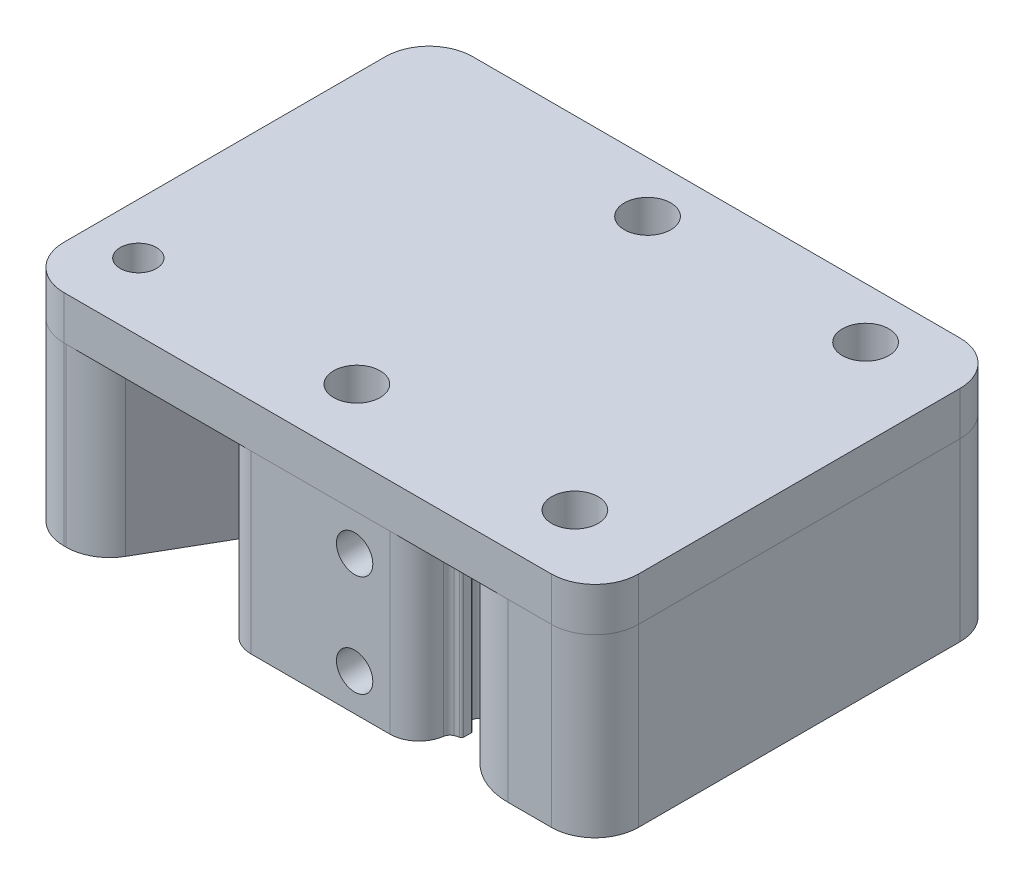
SolidWorks part; units mm, degrees
material "AISI 1045 Steel, cold drawn"
ref_plane "Front Plane" through (0, 0, 0) normal (0, 0, 1) x (1, 0, 0)
ref_plane "Top Plane" through (0, 0, 0) normal (0, 1, 0) x (1, 0, 0)
ref_plane "Right Plane" through (0, 0, 0) normal (1, 0, 0) x (0, 0, -1)
sketch "Sketch1" plane through (0, 0, 0) normal (0, 1, 0) x (1, 0, 0)
  line L0 (-13.5, -13.5) -> (-13.5, -14.619)
  line L1 (7.5, -10) -> (-7.5, -10) construction
  line L2 (7.5, -10) -> (7.5, 10) construction
  line L3 (7.5, 10) -> (-7.5, 10) construction
  line L4 (-7.5, -10) -> (-7.5, 10) construction
  line L5 (7.5, -10) -> (-7.5, 10) construction
  line L6 (7.5, 10) -> (-7.5, -10) construction
  line L7 (13.5, -13.5) -> (-13.5, -13.5) construction
  line L8 (13.5, -13.5) -> (13.5, 13.5)
  line L9 (13.5, 13.5) -> (-13.5, 13.5)
  line L10 (-13.5, -13.5) -> (-13.5, 13.5)
  line L11 (13.5, -13.5) -> (-13.5, 13.5) construction
  line L12 (13.5, 13.5) -> (-13.5, -13.5) construction
  line L13 (-13.5, -14.619) -> (13.5, -14.619)
  line L14 (13.5, -14.619) -> (13.5, -13.5)
  point P0 (0, 0)
  point P6 (0, 0)
  dimension "D1" = 15
  dimension "D2" = 27
  dimension "D3" = 1.119
  dimension "D4" = 20
extrude "Boss-Extrude1" add sketch "Sketch1" along normal mid plane 12.1
hole_wizard "M3 Clearance Hole1" positions "Sketch2" profile "Sketch3" hole size "M3" standard "ANSI Metric" end condition through all
sketch "Sketch2" plane through (0, 6.05, 0) normal (0, 1, 0) x (1, 0, 0)
  point P0 (-7.5, 10)
  point P3 (7.5, 10)
  point P6 (7.5, -10)
  point P9 (-7.5, -10)
sketch "Sketch3" plane through (-7.5, 6.05, -10) normal (1, 0, 0) x (0, 0, 1)
  line L0 (0, 0) -> (0, 12.1)
  line L1 (0, 12.1) -> (1.6, 12.1)
  line L2 (1.6, 12.1) -> (1.6, 0)
  line L5 (1.6, 0) -> (0, 0)
  line L11 (0, -6.35) -> (0, 107.95) construction
  dimension "Thru Hole Dia." = 3.2
  dimension "Thru Hole Depth" = 12.1
sketch "Sketch6" plane through (0, 6.05, 0) normal (0, 1, 0) x (1, 0, 0)
  line L0 (13.5, 13.5) -> (-13.5, 13.5) construction
  line L1 (-13.5, -14.619) -> (-28, -14.619)
  line L2 (-13.5, -14.619) -> (-13.5, 13.5)
  line L3 (-13.5, 13.5) -> (-28, 13.5)
  line L4 (-28, -14.619) -> (-28, 13.5)
  dimension "D1" = 28
extrude "Boss-Extrude3" add sketch "Sketch6" against normal up to surface (12.1 mm away) up to face at (-7.5, -6.05, -8.4)
sketch "Sketch8" plane through (0, 6.05, 0) normal (0, 1, 0) x (1, 0, 0)
  line L0 (-28, -14.619) -> (13.5, -14.619) construction
  line L2 (2.881, -10) -> (2.881, 4)
  line L3 (2.881, 4) -> (1.361, 4)
  line L4 (1.361, -14.619) -> (1.361, 4)
  line L5 (7.5, -14.619) -> (1.361, -14.619)
  arc A0 (2.881, -10) -> (7.5, -14.619) centre (7.5, -10) ccw
  dimension "D1" = 1.52
  dimension "D2" = 14
extrude "Cut-Extrude2" cut sketch "Sketch8" against normal up to surface (12.1 mm away) up to face at (-7.5, -6.05, -8.4)
sketch "Sketch9" plane through (0, 6.05, 0) normal (0, 1, 0) x (1, 0, 0)
  line L1 (2.881, 4) -> (6.306, 4)
  line L2 (2.881, 4) -> (2.881, -8)
  line L3 (2.881, -8) -> (6.306, -8)
  line L4 (6.306, 4) -> (6.306, -8)
  dimension "D1" = 3.425
  dimension "D2" = 12
extrude "Cut-Extrude3" cut sketch "Sketch9" against normal up to surface (12.1 mm away) up to face at (-7.5, -6.05, -8.4)
sketch "Sketch11" plane through (0, 6.05, 0) normal (0, 1, 0) x (1, 0, 0)
  line L1 (2.111, 0.7046) -> (2.111, 4.8734) construction
  line L4 (2.365, -998.8465) -> (2.365, 49001.1535) construction
  line L5 (2.111, 2.2598) -> (2.111, 2)
  line L6 (1.361, 3) -> (2.111, 3) construction
  line L7 (1.361, 4) -> (1.361, -14.619) construction
  line L8 (6.306, 4) -> (1.361, 4) construction
  line L9 (2.111, 2) -> (1.361, 2)
  line L10 (1.361, 2) -> (1.361, 4)
  line L11 (2.111, 4) -> (1.361, 4)
  line L12 (2.111, 3.7402) -> (2.111, 4)
  arc A2 (1.6728, 3.4989) -> (1.6728, 2.5011) centre (1.916, 3) ccw
  arc A4 (1.6728, 2.5011) -> (1.9806, 2.4085) centre (2.111, 3.4) ccw
  arc A5 (2.111, 2.2598) -> (1.9806, 2.4085) centre (1.961, 2.2598) ccw
  arc A6 (2.111, 3.7402) -> (1.9806, 3.5915) centre (1.961, 3.7402) cw
  arc A7 (1.6728, 3.4989) -> (1.9806, 3.5915) centre (2.111, 2.6) cw
  point P7 (1.361, 3)
  line M19 (1.361, -14.619) -> (1.361, 4)
  line M20 (1.361, 4) -> (6.306, 4)
  dimension "D3" = 0.555
  dimension "D4" = 1
  dimension "D5" = 1
  dimension "D6" = 0.15
  dimension "D1" = 0.254
  dimension "D2" = 0.75
  dimension "D7" = 1
extrude "Boss-Extrude4" add sketch "Sketch11" against normal up to surface (12.1 mm away) contours A2 A7 A6 L12 L10 M20 | L5 A5 A4 A2 L9 M19 region at (1.6833, 6.05, -3.7249) region at (1.6833, 6.05, -2.2751) up to face at (-7.5, -6.05, -8.4)
pattern_linear "LPattern1" count 9 spacing 2 along (0, 0, 1) of "Boss-Extrude4"
sketch "Sketch12" plane through (0, 6.05, 0) normal (0, 1, 0) x (1, 0, 0)
  circle A0 centre (2.111, 4) radius 0.5
  circle A1 centre (6.306, 4) radius 0.5
  circle A2 centre (6.306, -8) radius 0.5
  dimension "D1" = 1
extrude "Cut-Extrude5" cut sketch "Sketch12" against normal up to surface (12.1 mm away) up to face at (1.556, -6.05, 5.2005)
sketch "Sketch13" plane through (0, 6.05, 0) normal (0, 1, 0) x (1, 0, 0)
  line L3 (2.111, -14) -> (1.361, -14) construction
  line L4 (2.111, -13.7402) -> (2.111, -14) construction
  line L5 (2.111, -14) -> (1.361, -14)
  line L6 (2.111, -13.7402) -> (2.111, -14)
  line L7 (1.361, -14) -> (1.361, -13)
  arc A6 (1.6728, -12.5011) -> (1.6728, -13.4989) centre (1.916, -13) ccw construction
  arc A7 (1.6728, -13.4989) -> (1.9806, -13.5915) centre (2.111, -12.6) ccw construction
  arc A8 (2.111, -13.7402) -> (1.9806, -13.5915) centre (1.961, -13.7402) ccw construction
  arc A9 (1.361, -13) -> (1.6728, -13.4989) centre (1.916, -13) ccw
  arc A10 (1.6728, -13.4989) -> (1.9806, -13.5915) centre (2.111, -12.6) ccw
  arc A11 (2.111, -13.7402) -> (1.9806, -13.5915) centre (1.961, -13.7402) ccw
extrude "Cut-Extrude6" cut sketch "Sketch13" against normal up to surface (12.1 mm away) up to face at (1.6903, -6.05, 5.2284)
fillet "Fillet3" radius 0.5 7 edges at (5.806, 0, 8) (6.306, 0, 7.5) (5.806, 0, -4) (6.306, 0, -3.5) (2.611, 0, -4) (1.8595, 0, -3.5679) (2.881, 0, 8)
sketch "Sketch17" plane through (0, 6.05, 0) normal (0, 1, 0) x (1, 0, 0)
  line L0 (-21.1595, -14.619) -> (-15.513, -17.879)
  line L11 (-6.4019, 5.9019) -> (-3.8038, 4.4019) construction
  line L12 (-6.4019, 5.9019) -> (-2.9019, 11.9641) construction
  line L13 (-3.8038, 4.4019) -> (-0.3038, 10.4641) construction
  line L14 (-2.9019, 11.9641) -> (-0.3038, 10.4641) construction
  line L15 (-4.201, 12.7141) -> (0.9952, 9.7141) construction
  line L16 (-4.201, 12.7141) -> (-2.701, 15.3122) construction
  line L17 (0.9952, 9.7141) -> (2.4952, 12.3122) construction
  line L18 (-2.701, 15.3122) -> (2.4952, 12.3122) construction
  line L19 (-5.1029, 5.1519) -> (-0.1029, 13.8122) construction
  line L20 (-21.1595, -14.619) -> (-8.5843, 7.1619)
  line L21 (-15.513, -17.879) -> (-2.9378, 3.9019)
  line L22 (-8.5843, 7.1619) -> (-2.9378, 3.9019)
  line L23 (-22.5782, -10.8263) -> (-19.8719, -12.3888) construction
  line L24 (-22.5782, -10.8263) -> (-12.5782, 6.4942) construction
  line L25 (-19.8719, -12.3888) -> (-9.8719, 4.9317) construction
  line L26 (-12.5782, 6.4942) -> (-9.8719, 4.9317) construction
  line L27 (-28, -14.619) -> (1.361, -14.619) construction
  line L28 (-14.8719, -3.7285) -> (-17.5782, -2.166) construction
  circle A0 centre (-7.5, 10) radius 1.6 construction
  circle A1 centre (-7.5, -10) radius 1.6 construction
  dimension "D1" = 6.52
  dimension "D3" = 3
  dimension "D10" = 3
  dimension "D2" = 6
  dimension "D4" = 3
  dimension "D5" = 10
  dimension "D6" = 3.125
  dimension "D7" = 2.5
  dimension "D8" = 60
  dimension "D9" = 3
  dimension "D11" = 20
extrude "Cut-Extrude7" cut sketch "Sketch17" against normal up to surface (12.1 mm away) up to face at (1.9594, -6.05, 4.4571)
sketch "Sketch18" plane through (0, 6.05, 0) normal (0, 1, 0) x (1, 0, 0)
  line L0 (-26.0342, -14.619) -> (-26.0342, -10)
  line L2 (-14.1485, 10.3744) -> (-26.7237, -11.4065)
  line L3 (-12.344, 13.5) -> (-24.1063, -6.8729)
  line L4 (-12.344, 13.5) -> (-28, 13.5)
  line L5 (-28, 13.5) -> (-28, -14.619)
  line L7 (-28, -14.619) -> (-21.1595, -14.619) construction
  line L8 (-8.5843, 7.1619) -> (-21.1595, -14.619) construction
  line L10 (-28, -14.619) -> (-26.0342, -14.619)
  arc A2 (-24.1063, -6.8729) -> (-26.0342, -10) centre (-22.5342, -10) ccw
  point P0 (-7.5, -10)
  dimension "D2" = 3.5
  dimension "D1" = 6.425
extrude "Cut-Extrude8" cut sketch "Sketch18" against normal up to surface (12.1 mm away) contours A2 L10 | A2 L3 L4 L5 L10 region at (-22.8632, 6.05, -4.1187) up to face at (1.2277, -6.05, 4.4618)
hole_wizard "M3 Clearance Hole2" positions "Sketch19" profile "Sketch20" hole size "M3" standard "ANSI Metric" end condition up to next
sketch "Sketch19" plane through (0, 6.05, 0) normal (0, 1, 0) x (1, 0, 0)
  point P0 (-22.5342, -10)
sketch "Sketch20" plane through (-22.5342, 6.05, 10) normal (1, 0, 0) x (0, 0, 1)
  line L0 (0, 0) -> (0, 12.1)
  line L1 (0, 12.1) -> (1.6, 12.1)
  line L2 (1.6, 12.1) -> (1.6, 0)
  line L5 (1.6, 0) -> (0, 0)
  line L11 (0, -6.35) -> (0, 107.95) construction
  dimension "Thru Hole Dia." = 3.2
  dimension "Thru Hole Depth" = 12.1
fillet "Fillet4" radius 3 5 edges at (13.5, 0, 14.619) (13.5, 0, -13.5) (-12.344, 0, -13.5) (-26.0342, 0, 14.619) (-21.1595, 0, 14.619)
sketch "Sketch21" plane through (0, 6.05, 0) normal (0, 1, 0) x (1, 0, 0)
  line L0 (-8.5843, 7.1619) -> (-20.2935, -13.119) construction
  line L1 (-17.8343, -8.8595) -> (-20.8004, -7.147)
  line L2 (-17.8343, -8.8595) -> (-9.3343, 5.8629)
  line L3 (-20.8004, -7.147) -> (-12.3004, 7.5754)
  line L4 (-9.3343, 5.8629) -> (-12.3004, 7.5754)
  line L5 (-2.9378, 3.9019) -> (-8.5843, 7.1619) construction
  dimension "D3" = 17
  dimension "D1" = 3.425
  dimension "D2" = 1.5
extrude "Cut-Extrude9" cut sketch "Sketch21" against normal up to surface (12.1 mm away) up to face at (-22.5342, -6.05, 11.6)
sketch "Sketch22" plane through (0, 6.05, 0) normal (0, 1, 0) x (1, 0, 0)
  circle A0 centre (-20.8004, -7.147) radius 0.5
  circle A1 centre (-12.3004, 7.5754) radius 0.5
  circle A2 centre (-8.5843, 7.1619) radius 0.5
  circle A3 centre (-2.9378, 3.9019) radius 0.5
  arc A4 (2.544, 4.25) -> (1.6303, 3.8625) centre (2.111, 4) ccw construction
extrude "Cut-Extrude10" cut sketch "Sketch22" against normal up to surface (12.1 mm away) up to face at (-22.5342, -6.05, 11.6)
fillet "Fillet5" radius 0.5 10 edges at (-17.8343, 0, 8.8595) (-3.1878, 0, -3.4689) (-3.3708, 0, -4.1519) (-8.8343, 0, -6.7289) (-8.1513, 0, -6.9119) (-11.8674, 0, -7.3254) (-12.5504, 0, -7.1424) (-20.5504, 0, 6.714) (-20.3674, 0, 7.397) (-9.3343, 0, -5.8629)
ref_plane "Plane2" through (6.9551, 0, -12.0466) normal (0.5, 0, -0.866) x (-0.866, 0, -0.5)
hole_wizard "CBORE for M3 SHCS1" positions "Sketch23" profile "Sketch25" counterbore size "M3" standard "ANSI Metric" end condition up to next
sketch "Sketch23" plane through (6.9551, 0, -12.0466) normal (0.5, 0, -0.866) x (-0.866, 0, -0.5)
  line L0 (4.4952, -6.05) -> (9.4952, 6.05) construction
  line L1 (-2.3433, -6.05) -> (15.9402, -6.05) construction
  line L3 (-2.3433, 6.05) -> (15.9402, 6.05) construction
  point P15 (6.9952, 0)
  dimension "D1" = 5
sketch "Sketch25" plane through (0.8971, 0, -15.5442) normal (0, 1, 0) x (-0.866, 0, -0.5)
  line L0 (0, 0) -> (0, 12)
  line L1 (0, 12) -> (1.6, 12)
  line L3 (1.6, 12) -> (1.6, 6)
  line L4 (1.6, 6) -> (3.25, 6)
  line L5 (3.25, 6) -> (3.25, 0)
  line L7 (3.25, 0) -> (0, 0)
  line L11 (0, -6.35) -> (0, 107.95) construction
  dimension "Thru Hole Dia." = 3.2
  dimension "Thru Hole Depth" = 12
  dimension "C'Bore Dia." = 6.5
  dimension "C'Bore Depth" = 6
sketch "Sketch30" plane through (0, 6.05, 0) normal (0, 1, 0) x (1, 0, 0)
  line L1 (3.381, -8) -> (5.44, -8) construction
  line L2 (6.306, -7.134) -> (6.306, 3.134) construction
  line L3 (5.44, 4) -> (2.977, 4) construction
  line L4 (3.381, -8) -> (5.44, -8)
  line L5 (6.306, -7.134) -> (6.306, 3.134)
  line L6 (5.44, 4) -> (2.977, 4)
  line L7 (-18.0843, -9.2926) -> (-9.0843, 6.2959)
  line L8 (-20.0504, -7.5801) -> (-18.2673, -8.6095) construction
  line L9 (-12.7335, 6.8254) -> (-20.3674, -6.397) construction
  line L10 (-9.7673, 6.1129) -> (-11.5504, 7.1424) construction
  line L11 (-20.0504, -7.5801) -> (-18.2673, -8.6095)
  line L12 (-12.7335, 6.8254) -> (-20.3674, -6.397)
  line L13 (-9.7673, 6.1129) -> (-11.5504, 7.1424)
  line L14 (2.881, -8.5) -> (2.881, 4.0093)
  arc A0 (3.381, -8) -> (2.881, -8.5) centre (3.381, -8.5) ccw construction
  arc A1 (5.873, -8.25) -> (5.44, -8) centre (5.44, -8.5) ccw construction
  arc A2 (5.873, -8.25) -> (6.556, -7.567) centre (6.306, -8) ccw construction
  arc A3 (6.306, -7.134) -> (6.556, -7.567) centre (6.806, -7.134) ccw construction
  arc A4 (6.556, 3.567) -> (6.306, 3.134) centre (6.806, 3.134) ccw construction
  arc A5 (6.556, 3.567) -> (5.873, 4.25) centre (6.306, 4) ccw construction
  arc A6 (5.44, 4) -> (5.873, 4.25) centre (5.44, 4.5) ccw construction
  arc A7 (2.544, 4.25) -> (2.977, 4) centre (2.977, 4.5) ccw construction
  arc A8 (3.381, -8) -> (2.881, -8.5) centre (3.381, -8.5) ccw
  arc A9 (5.873, -8.25) -> (5.44, -8) centre (5.44, -8.5) ccw
  arc A10 (5.873, -8.25) -> (6.556, -7.567) centre (6.306, -8) ccw
  arc A11 (6.306, -7.134) -> (6.556, -7.567) centre (6.806, -7.134) ccw
  arc A12 (6.556, 3.567) -> (6.306, 3.134) centre (6.806, 3.134) ccw
  arc A13 (6.556, 3.567) -> (5.873, 4.25) centre (6.306, 4) ccw
  arc A14 (5.44, 4) -> (5.873, 4.25) centre (5.44, 4.5) ccw
  arc A15 (2.881, 4.0093) -> (2.977, 4) centre (2.977, 4.5) ccw
  arc A17 (-18.0843, -9.2926) -> (-18.2673, -8.6095) centre (-18.5173, -9.0426) ccw construction
  arc A18 (-20.0504, -7.5801) -> (-20.5504, -7.5801) centre (-20.3004, -8.0131) ccw construction
  arc A19 (-20.8004, -6.647) -> (-20.3674, -6.397) centre (-20.8004, -6.147) ccw construction
  arc A20 (-12.7335, 6.8254) -> (-12.7335, 7.3254) centre (-13.1665, 7.0754) ccw construction
  arc A21 (-11.8004, 7.5754) -> (-12.7335, 7.3254) centre (-12.3004, 7.5754) ccw construction
  arc A22 (-11.8004, 7.5754) -> (-11.5504, 7.1424) centre (-11.3004, 7.5754) ccw construction
  arc A23 (-9.7673, 6.1129) -> (-9.0843, 6.2959) centre (-9.5173, 6.5459) ccw construction
  arc A24 (-18.0843, -9.2926) -> (-18.2673, -8.6095) centre (-18.5173, -9.0426) ccw
  arc A25 (-20.0504, -7.5801) -> (-20.5504, -7.5801) centre (-20.3004, -8.0131) ccw
  arc A26 (-20.8004, -6.647) -> (-20.3674, -6.397) centre (-20.8004, -6.147) ccw
  arc A27 (-12.7335, 6.8254) -> (-12.7335, 7.3254) centre (-13.1665, 7.0754) ccw
  arc A28 (-11.8004, 7.5754) -> (-12.7335, 7.3254) centre (-12.3004, 7.5754) ccw
  arc A29 (-11.8004, 7.5754) -> (-11.5504, 7.1424) centre (-11.3004, 7.5754) ccw
  arc A30 (-9.7673, 6.1129) -> (-9.0843, 6.2959) centre (-9.5173, 6.5459) ccw
  arc A31 (-20.8004, -6.647) -> (-20.5504, -7.5801) centre (-20.8004, -7.147) ccw construction
  arc A32 (-20.8004, -6.647) -> (-20.5504, -7.5801) centre (-20.8004, -7.147) ccw
extrude "Boss-Extrude8" add sketch "Sketch30" against normal up to surface (12.1 mm away) up to face at (-22.5342, -6.05, 11.6)
fillet "Fillet6" radius 1 1 edges at (2.881, 0, -4.0093)
sketch "Sketch31" plane through (0, 6.05, 0) normal (0, 1, 0) x (1, 0, 0)
  line L0 (13.5, 6.9) -> (4.381, 6.9)
  line L2 (4.381, 6.9) -> (4.381, -6.9)
  line L3 (4.381, -6.9) -> (13.5, -6.9)
  line L4 (2.881, -10) -> (2.881, 3.4759) construction
  line L6 (13.5, 6.9) -> (13.5, -6.9)
  line L7 (13.5, -11.619) -> (13.5, 10.5) construction
  circle A0 centre (7.5, -10) radius 1.6 construction
  circle A1 centre (7.5, 10) radius 1.6 construction
  dimension "D1" = 3.1
  dimension "D2" = 3.1
  dimension "D3" = 1.5
extrude "Cut-Extrude11" cut sketch "Sketch31" against normal up to surface (12.1 mm away) up to face at (-0.8329, -6.05, 3.7569)
sketch "Sketch32" plane through (0, 6.05, 0) normal (0, 1, 0) x (1, 0, 0)
  line L0 (-10.0574, 7.6105) -> (-19.366, -8.5125)
  line L1 (-9.0173, 6.4119) -> (-20.2935, -13.119) construction
  line L2 (-13.21, 12) -> (-24.1063, -6.8729) construction
  line L3 (-13.21, 12) -> (-24.1063, -6.8729)
  line L5 (10.5, 13.5) -> (-10.6119, 13.5) construction
  line L6 (-7.5, 13.5) -> (-10.6119, 13.5)
  arc A0 (-19.366, -8.5125) -> (-24.1063, -6.8729) centre (-22.5342, -10) ccw
  arc A1 (-24.1063, -6.8729) -> (-26.0342, -10) centre (-22.5342, -10) ccw construction
  arc A2 (-7.5, 13.5) -> (-10.0574, 7.6105) centre (-7.5, 10) ccw
  arc A3 (-10.6119, 13.5) -> (-13.21, 12) centre (-10.6119, 10.5) ccw construction
  arc A4 (-10.6119, 13.5) -> (-13.21, 12) centre (-10.6119, 10.5) ccw
  dimension "D1" = 1.5
extrude "Cut-Extrude12" cut sketch "Sketch32" against normal up to surface (12.1 mm away) up to face at (-0.3561, -6.05, 3.5736)
sketch "Sketch34" plane through (0, -6.05, 0) normal (0, -1, 0) x (1, 0, 0)
  line L0 (0.111, -6.1826) -> (-7.4426, 6.9005)
  line L1 (-3.3708, -3.1519) -> (-13.6309, 14.619) construction
  line L2 (0.111, -6.1826) -> (0.111, 12.619)
  line L4 (0.111, 12.619) -> (-5.8414, 12.619)
  line L5 (2.111, 10.2598) -> (2.111, 9.7402) construction
  line L7 (-13.6309, 14.619) -> (1.361, 14.619) construction
  circle A2 centre (-7.5, 10) radius 3.1
  arc A3 (-7.4426, 6.9005) -> (-5.8414, 12.619) centre (-7.5, 10) ccw
  dimension "D2" = 1.5
  dimension "D3" = 2
  dimension "D4" = 2
  dimension "D1" = 1.5
extrude "Cut-Extrude14" cut sketch "Sketch34" against normal up to surface (12.1 mm away) up to face at (-0.2449, 6.05, 3.6119)
sketch "Sketch35" plane through (0, -6.05, 0) normal (0, -1, 0) x (1, 0, 0)
  line L0 (-4.9175, -11.9731) -> (0.7117, -8.7231) construction
  line L1 (-7.5622, -13.5) -> (1.2713, -8.4)
  line L2 (10.5, -13.5) -> (-7.5, -13.5) construction
  line L3 (1.2713, -8.4) -> (4.3871, -8.4)
  line L4 (7.5, -13.5) -> (-7.5622, -13.5)
  line L6 (4.381, -6.9) -> (13.5, -6.9) construction
  circle A1 centre (7.5, -10) radius 1.6 construction
  arc A3 (4.3871, -8.4) -> (7.5, -13.5) centre (7.5, -10) ccw
  dimension "D1" = 1.5
extrude "Cut-Extrude15" cut sketch "Sketch35" against normal up to surface (12.1 mm away) up to face at (-2.7337, 6.05, 6.3401)
fillet "Fillet7" radius 2 9 edges at (-13.6309, 0, 14.619) (1.361, 0, 14.619) (13.5, 0, 6.9) (4.381, 0, 6.9) (13.5, 0, -6.9) (4.381, 0, -6.9) (-19.366, 0, 8.5125) (-7.5612, 0, -13.4995) (-10.0574, 0, -7.6105)
fillet "Fillet8" radius 1 6 edges at (0.111, 0, 12.619) (0.111, 0, -6.1826) (-5.8414, 0, 12.619) (-7.4426, 0, 6.9005) (4.3871, 0, -8.4) (1.2713, 0, -8.4)
sketch "Sketch36" plane through (0, 6.05, 0) normal (0, 1, 0) x (1, 0, 0)
  line L0 (2.881, 4.4759) -> (2.881, 3.4759)
  line L1 (1.611, 4) -> (1.611, 4.4759)
  arc A0 (1.611, 4.4759) -> (2.881, 4.4759) centre (2.246, 4.4759) cw
  arc A3 (2.544, 4.25) -> (1.6303, 3.8625) centre (2.111, 4) ccw construction
  arc A4 (2.544, 4.25) -> (2.6117, 4.1586) centre (2.977, 4.5) ccw construction
  arc A5 (2.881, 3.4759) -> (2.6117, 4.1586) centre (1.881, 3.4759) ccw construction
  arc A6 (2.544, 4.25) -> (1.611, 4) centre (2.111, 4) ccw
  arc A7 (2.544, 4.25) -> (2.6117, 4.1586) centre (2.977, 4.5) ccw
  arc A8 (2.881, 3.4759) -> (2.6117, 4.1586) centre (1.881, 3.4759) ccw
  dimension "D1" = 1
extrude "Cut-Extrude16" cut sketch "Sketch36" against normal up to surface (12.1 mm away) up to face at (-2.9137, -6.05, 6.8822)
sketch "Sketch37" plane through (0, 6.05, 0) normal (0, 1, 0) x (1, 0, 0)
  line L0 (-10.6817, 6.5291) -> (-9.847, 7.9748)
  line L1 (-18.0522, -6.2369) -> (-10.6817, 6.5291) construction
  line L2 (1.0392, 8.534) -> (-6.9682, 13.1571) construction
  line L3 (-6.6764, 12.9886) -> (-6.9682, 13.1571)
  arc A0 (-6.6764, 12.9886) -> (-9.847, 7.9748) centre (-7.5, 10) ccw
  circle A1 centre (-7.5, 10) radius 1.6 construction
  arc A2 (-6.9682, 13.1571) -> (-8.5926, 13.3251) centre (-7.9682, 11.425) ccw construction
  arc A3 (-8.5926, 13.3251) -> (-10.6269, 8.4276) centre (-7.5, 10) ccw construction
  arc A4 (-10.6817, 6.5291) -> (-10.6269, 8.4276) centre (-12.4137, 7.5291) ccw construction
  arc A5 (-6.9682, 13.1571) -> (-8.5926, 13.3251) centre (-7.9682, 11.425) ccw
  arc A6 (-8.5926, 13.3251) -> (-10.6269, 8.4276) centre (-7.5, 10) ccw
  arc A7 (-10.6817, 6.5291) -> (-10.6269, 8.4276) centre (-12.4137, 7.5291) ccw
  dimension "D1" = 1.5
extrude "Cut-Extrude17" cut sketch "Sketch37" against normal up to surface (12.1 mm away) up to face at (-2.9137, -6.05, 6.8822)
fillet "Fillet9" radius 2 2 edges at (-6.6764, 0, -12.9886) (-9.847, 0, -7.9748)
sketch "Sketch38" plane through (0, 6.05, 0) normal (0, 1, 0) x (1, 0, 0)
  line L0 (-26.0342, -10) -> (-26.0342, 13.1)
  line L1 (-26.0342, 13.1) -> (-7.5, 13.1)
  line L2 (-24.5342, -7.1277) -> (-24.5342, 11.6)
  line L3 (-24.5342, 11.6) -> (-10.1552, 11.6)
  line L4 (-24.5342, -10) -> (-24.5342, 11.6) construction
  line L5 (-24.5342, 11.6) -> (-7.5, 11.6) construction
  arc A0 (-7.2093, 13.0863) -> (-10.3388, 8.7545) centre (-7.5, 10) ccw construction
  arc A1 (-7.5, 13.1) -> (-10.1552, 11.6) centre (-7.5, 10) ccw
  arc A2 (-20.7842, -6.9689) -> (-26.0342, -10) centre (-22.5342, -10) ccw construction
  arc A3 (-24.5342, -7.1277) -> (-26.0342, -10) centre (-22.5342, -10) ccw
  dimension "D1" = 1.5
extrude "Boss-Extrude9" add sketch "Sketch38" against normal up to surface (12.1 mm away) up to face at (-2.9137, -6.05, 6.8822)
fillet "Fillet10" radius 2 4 edges at (-24.5342, 0, 7.1277) (-10.1552, 0, -11.6) (-26.0342, 0, -13.1) (-24.5342, 0, -11.6)
sketch "Sketch39" plane through (0.9551, 0, -1.6543) normal (-0.5, 0, 0.866) x (0.866, 0, 0.5)
  circle A0 centre (-6.9952, 0) radius 1.6 construction
  circle A1 centre (-6.9952, 0) radius 1.6
extrude "Boss-Extrude10" add sketch "Sketch39" against normal up to surface (6 mm away)
sketch "Sketch40" plane through (0, 6.05, 0) normal (0, 1, 0) x (1, 0, 0)
  line L0 (-22.5342, 11.6) -> (-12.5843, 11.6) construction
  line L1 (-24.5342, -4.5) -> (-24.5342, 9.6) construction
  line L2 (-18.0522, -6.2369) -> (-10.4382, 6.9509) construction
  line L3 (-22.5342, 11.6) -> (-12.5843, 11.6)
  line L4 (-24.5342, -4.5) -> (-24.5342, 9.6)
  line L5 (-18.0522, -6.2369) -> (-10.4382, 6.9509)
  line L6 (0.111, 2.4506) -> (0.111, -11.619) construction
  line L7 (-0.889, -12.619) -> (-3.7332, -12.619) construction
  line L8 (-6.7643, -5.7258) -> (-1.755, 2.9506) construction
  line L9 (0.111, 2.4506) -> (0.111, -11.619)
  line L10 (-0.889, -12.619) -> (-3.7332, -12.619)
  line L11 (-6.7643, -5.7258) -> (-1.755, 2.9506)
  line L12 (6.381, -6.9) -> (11.5, -6.9) construction
  line L13 (4.381, 4.9) -> (4.381, -4.9) construction
  line L14 (11.5, 6.9) -> (6.381, 6.9) construction
  line L15 (6.381, -6.9) -> (11.5, -6.9)
  line L16 (4.381, 4.9) -> (4.381, -4.9)
  line L17 (11.5, 6.9) -> (6.381, 6.9)
  line L18 (13.5, 8.9) -> (13.5, -8.9)
  arc A0 (-10.4382, 6.9509) -> (-10.3388, 8.7545) centre (-12.1702, 7.9509) ccw construction
  arc A1 (-10.5905, 9.7569) -> (-10.3388, 8.7545) centre (-7.5, 10) ccw construction
  arc A2 (-10.5905, 9.7569) -> (-12.5843, 11.6) centre (-12.5843, 9.6) ccw construction
  arc A3 (-22.5342, 11.6) -> (-24.5342, 9.6) centre (-22.5342, 9.6) ccw construction
  arc A4 (-24.5342, -4.5) -> (-22.5342, -6.5) centre (-22.5342, -4.5) ccw construction
  arc A5 (-20.7842, -6.9689) -> (-22.5342, -6.5) centre (-22.5342, -10) ccw construction
  arc A6 (-20.7842, -6.9689) -> (-18.0522, -6.2369) centre (-19.7842, -5.2369) ccw construction
  arc A7 (-10.4382, 6.9509) -> (-10.3388, 8.7545) centre (-12.1702, 7.9509) ccw
  arc A8 (-10.5905, 9.7569) -> (-10.3388, 8.7545) centre (-7.5, 10) ccw
  arc A9 (-10.5905, 9.7569) -> (-12.5843, 11.6) centre (-12.5843, 9.6) ccw
  arc A10 (-22.5342, 11.6) -> (-24.5342, 9.6) centre (-22.5342, 9.6) ccw
  arc A11 (-24.5342, -4.5) -> (-22.5342, -6.5) centre (-22.5342, -4.5) ccw
  arc A12 (-20.7842, -6.9689) -> (-22.5342, -6.5) centre (-22.5342, -10) ccw
  arc A13 (-20.7842, -6.9689) -> (-18.0522, -6.2369) centre (-19.7842, -5.2369) ccw
  arc A14 (0.111, 2.4506) -> (-1.755, 2.9506) centre (-0.889, 2.4506) ccw construction
  arc A15 (-0.889, -12.619) -> (0.111, -11.619) centre (-0.889, -11.619) ccw construction
  arc A16 (-4.6519, -11.2241) -> (-3.7332, -12.619) centre (-3.7332, -11.619) ccw construction
  arc A17 (-4.6519, -11.2241) -> (-6.289, -7.1463) centre (-7.5, -10) ccw construction
  arc A18 (-6.7643, -5.7258) -> (-6.289, -7.1463) centre (-5.8983, -6.2258) ccw construction
  arc A19 (0.111, 2.4506) -> (-1.755, 2.9506) centre (-0.889, 2.4506) ccw
  arc A20 (-0.889, -12.619) -> (0.111, -11.619) centre (-0.889, -11.619) ccw
  arc A21 (-4.6519, -11.2241) -> (-3.7332, -12.619) centre (-3.7332, -11.619) ccw
  arc A22 (-4.6519, -11.2241) -> (-6.289, -7.1463) centre (-7.5, -10) ccw
  arc A23 (-6.7643, -5.7258) -> (-6.289, -7.1463) centre (-5.8983, -6.2258) ccw
  arc A24 (13.5, -8.9) -> (11.5, -6.9) centre (11.5, -8.9) ccw construction
  arc A25 (4.381, -4.9) -> (6.381, -6.9) centre (6.381, -4.9) ccw construction
  arc A26 (6.381, 6.9) -> (4.381, 4.9) centre (6.381, 4.9) ccw construction
  arc A27 (11.5, 6.9) -> (13.5, 8.9) centre (11.5, 8.9) ccw construction
  arc A28 (13.5, -8.9) -> (11.5, -6.9) centre (11.5, -8.9) ccw
  arc A29 (4.381, -4.9) -> (6.381, -6.9) centre (6.381, -4.9) ccw
  arc A30 (6.381, 6.9) -> (4.381, 4.9) centre (6.381, 4.9) ccw
  arc A31 (11.5, 6.9) -> (13.5, 8.9) centre (11.5, 8.9) ccw
extrude "Boss-Extrude11" add sketch "Sketch40" against normal up to surface (12.1 mm away) up to face at (-17.7037, -6.05, -3.3974)
sketch "Sketch41" plane through (0, 6.05, 0) normal (0, 1, 0) x (1, 0, 0)
  line L0 (10.5, 13.5) -> (-23.0342, 13.5)
  line L22 (13.5, -11.619) -> (13.5, 10.5)
  line L23 (10.5, 13.5) -> (7.5, 13.5)
  line L24 (3.0402, 8.4) -> (1.5392, 8.4)
  line L25 (1.0392, 8.534) -> (-6.3969, 12.8272)
  line L26 (-7.5, 13.1) -> (-24.0342, 13.1)
  line L27 (-26.0342, 11.1) -> (-26.0342, -11.619)
  line L28 (-23.0342, -14.619) -> (-22.8916, -14.619)
  line L29 (-20.2935, -13.119) -> (-9.0173, 6.4119)
  line L30 (-7.8343, 6.7289) -> (-3.6878, 4.3349)
  line L31 (-3.3708, 3.1519) -> (-11.8988, -11.619)
  line L32 (-10.1668, -14.619) -> (-0.6104, -14.619)
  line L33 (2.111, -12.2598) -> (2.111, -11.7402)
  line L34 (2.111, -10.2598) -> (2.111, -9.7402)
  line L35 (2.111, -8.2598) -> (2.111, -7.7402)
  line L36 (2.111, -6.2598) -> (2.111, -5.7402)
  line L37 (2.111, -4.2598) -> (2.111, -3.7402)
  line L38 (2.111, -2.2598) -> (2.111, -1.7402)
  line L39 (2.111, -0.2598) -> (2.111, 0.2598)
  line L40 (2.111, 1.7402) -> (2.111, 2.2598)
  line L41 (1.611, 4) -> (1.611, 4.4759)
  line L42 (2.881, 4.4759) -> (2.881, -10)
  line L43 (7.5, -14.619) -> (10.5, -14.619)
  line L44 (13.5, -11.619) -> (13.5, 10.5)
  line L49 (-26.0342, 10.5) -> (-26.0342, -11.619)
  line L50 (-23.0342, -14.619) -> (-22.8916, -14.619)
  line L65 (-22.8916, -14.619) -> (10.5, -14.619)
  circle A2 centre (7.5, 10) radius 1.6 construction
  circle A3 centre (-7.5, 10) radius 1.6 construction
  circle A6 centre (7.5, 10) radius 1.6
  circle A7 centre (-7.5, 10) radius 1.6
  circle A8 centre (7.5, -10) radius 1.6 construction
  circle A9 centre (7.5, -10) radius 1.6
  circle A10 centre (-7.5, -10) radius 1.6 construction
  circle A11 centre (-7.5, -10) radius 1.6
  arc A12 (-23.0342, 13.5) -> (-26.0342, 10.5) centre (-23.0342, 10.5) ccw
  circle A13 centre (-22.5342, -10) radius 1.25
  arc A63 (13.5, 10.5) -> (10.5, 13.5) centre (10.5, 10.5) ccw
  arc A64 (7.5, 13.5) -> (4.0313, 9.5333) centre (7.5, 10) ccw
  arc A65 (3.0402, 8.4) -> (4.0313, 9.5333) centre (3.0402, 9.4) ccw
  arc A66 (1.0392, 8.534) -> (1.5392, 8.4) centre (1.5392, 9.4) ccw
  arc A67 (-6.3969, 12.8272) -> (-7.2093, 13.0863) centre (-7.3969, 11.0952) ccw
  arc A68 (-7.2093, 13.0863) -> (-7.5, 13.1) centre (-7.5, 10) ccw
  arc A69 (-24.0342, 13.1) -> (-26.0342, 11.1) centre (-24.0342, 11.1) ccw
  arc A70 (-26.0342, -11.619) -> (-23.0342, -14.619) centre (-23.0342, -11.619) ccw
  arc A71 (-22.8916, -14.619) -> (-20.2935, -13.119) centre (-22.8916, -11.619) ccw
  arc A72 (-9.0173, 6.4119) -> (-9.0173, 6.9119) centre (-9.4503, 6.6619) ccw
  arc A73 (-8.0843, 7.1619) -> (-9.0173, 6.9119) centre (-8.5843, 7.1619) ccw
  arc A74 (-8.0843, 7.1619) -> (-7.8343, 6.7289) centre (-7.5843, 7.1619) ccw
  arc A75 (-3.6878, 4.3349) -> (-3.1878, 4.3349) centre (-3.4378, 4.7679) ccw
  arc A76 (-2.9378, 3.4019) -> (-3.1878, 4.3349) centre (-2.9378, 3.9019) ccw
  arc A77 (-2.9378, 3.4019) -> (-3.3708, 3.1519) centre (-2.9378, 2.9019) ccw
  arc A78 (-11.8988, -11.619) -> (-10.1668, -14.619) centre (-10.1668, -12.619) ccw
  arc A79 (-0.6104, -14.619) -> (1.3672, -12.9172) centre (-0.6104, -12.619) ccw
  arc A80 (1.6728, -12.5011) -> (1.3672, -12.9172) centre (1.916, -13) ccw
  arc A81 (1.9806, -12.4085) -> (1.6728, -12.5011) centre (2.111, -13.4) ccw
  arc A82 (1.9806, -12.4085) -> (2.111, -12.2598) centre (1.961, -12.2598) ccw
  arc A83 (2.111, -11.7402) -> (1.9806, -11.5915) centre (1.961, -11.7402) ccw
  arc A84 (1.6728, -11.4989) -> (1.9806, -11.5915) centre (2.111, -10.6) ccw
  arc A85 (1.6728, -10.5011) -> (1.6728, -11.4989) centre (1.916, -11) ccw
  arc A86 (1.9806, -10.4085) -> (1.6728, -10.5011) centre (2.111, -11.4) ccw
  arc A87 (1.9806, -10.4085) -> (2.111, -10.2598) centre (1.961, -10.2598) ccw
  arc A88 (2.111, -9.7402) -> (1.9806, -9.5915) centre (1.961, -9.7402) ccw
  arc A89 (1.6728, -9.4989) -> (1.9806, -9.5915) centre (2.111, -8.6) ccw
  arc A90 (1.6728, -8.5011) -> (1.6728, -9.4989) centre (1.916, -9) ccw
  arc A91 (1.9806, -8.4085) -> (1.6728, -8.5011) centre (2.111, -9.4) ccw
  arc A92 (1.9806, -8.4085) -> (2.111, -8.2598) centre (1.961, -8.2598) ccw
  arc A93 (2.111, -7.7402) -> (1.9806, -7.5915) centre (1.961, -7.7402) ccw
  arc A94 (1.6728, -7.4989) -> (1.9806, -7.5915) centre (2.111, -6.6) ccw
  arc A95 (1.6728, -6.5011) -> (1.6728, -7.4989) centre (1.916, -7) ccw
  arc A96 (1.9806, -6.4085) -> (1.6728, -6.5011) centre (2.111, -7.4) ccw
  arc A97 (1.9806, -6.4085) -> (2.111, -6.2598) centre (1.961, -6.2598) ccw
  arc A98 (2.111, -5.7402) -> (1.9806, -5.5915) centre (1.961, -5.7402) ccw
  arc A99 (1.6728, -5.4989) -> (1.9806, -5.5915) centre (2.111, -4.6) ccw
  arc A100 (1.6728, -4.5011) -> (1.6728, -5.4989) centre (1.916, -5) ccw
  arc A101 (1.9806, -4.4085) -> (1.6728, -4.5011) centre (2.111, -5.4) ccw
  arc A102 (1.9806, -4.4085) -> (2.111, -4.2598) centre (1.961, -4.2598) ccw
  arc A103 (2.111, -3.7402) -> (1.9806, -3.5915) centre (1.961, -3.7402) ccw
  arc A104 (1.6728, -3.4989) -> (1.9806, -3.5915) centre (2.111, -2.6) ccw
  arc A105 (1.6728, -2.5011) -> (1.6728, -3.4989) centre (1.916, -3) ccw
  arc A106 (1.9806, -2.4085) -> (1.6728, -2.5011) centre (2.111, -3.4) ccw
  arc A107 (1.9806, -2.4085) -> (2.111, -2.2598) centre (1.961, -2.2598) ccw
  arc A108 (2.111, -1.7402) -> (1.9806, -1.5915) centre (1.961, -1.7402) ccw
  arc A109 (1.6728, -1.4989) -> (1.9806, -1.5915) centre (2.111, -0.6) ccw
  arc A110 (1.6728, -0.5011) -> (1.6728, -1.4989) centre (1.916, -1) ccw
  arc A111 (1.9806, -0.4085) -> (1.6728, -0.5011) centre (2.111, -1.4) ccw
  arc A112 (1.9806, -0.4085) -> (2.111, -0.2598) centre (1.961, -0.2598) ccw
  arc A113 (2.111, 0.2598) -> (1.9806, 0.4085) centre (1.961, 0.2598) ccw
  arc A114 (1.6728, 0.5011) -> (1.9806, 0.4085) centre (2.111, 1.4) ccw
  arc A115 (1.6728, 1.4989) -> (1.6728, 0.5011) centre (1.916, 1) ccw
  arc A116 (1.9806, 1.5915) -> (1.6728, 1.4989) centre (2.111, 0.6) ccw
  arc A117 (1.9806, 1.5915) -> (2.111, 1.7402) centre (1.961, 1.7402) ccw
  arc A118 (2.111, 2.2598) -> (1.9806, 2.4085) centre (1.961, 2.2598) ccw
  arc A119 (1.6728, 2.5011) -> (1.9806, 2.4085) centre (2.111, 3.4) ccw
  arc A120 (1.5128, 3.3814) -> (1.6728, 2.5011) centre (1.916, 3) ccw
  arc A121 (1.5128, 3.3814) -> (1.6303, 3.8625) centre (1.1496, 3.725) ccw
  arc A122 (1.611, 4) -> (1.6303, 3.8625) centre (2.111, 4) ccw
  arc A123 (2.881, 4.4759) -> (1.611, 4.4759) centre (2.246, 4.4759) ccw
  arc A124 (2.881, -10) -> (7.5, -14.619) centre (7.5, -10) ccw
  arc A125 (10.5, -14.619) -> (13.5, -11.619) centre (10.5, -11.619) ccw
  arc A126 (13.5, 10.5) -> (10.5, 13.5) centre (10.5, 10.5) ccw
  arc A133 (-26.0342, -11.619) -> (-23.0342, -14.619) centre (-23.0342, -11.619) ccw
  arc A188 (10.5, -14.619) -> (13.5, -11.619) centre (10.5, -11.619) ccw
  dimension "D2" = 3
  dimension "D3" = 2.5
  dimension "D1" = 0
extrude "Boss-Extrude12" add sketch "Sketch41" along normal blind 3 separate body
hole_wizard "M3x0.5 Tapped Hole1" positions "Sketch42" profile "Sketch43" tap size "M3x0.5" standard "ANSI Metric"
sketch "Sketch42" plane through (0, 0, 14.619) normal (0, 0, 1) x (1, 0, 0)
  line L0 (-3.0342, 3.5) -> (-3.0342, -3.5) construction
  line L2 (-26.0342, -6.05) -> (-26.0342, 6.05) construction
  point P0 (-3.0342, 3.5)
  point P2 (-3.0342, -3.5)
  point P9 (-3.0342, 0)
  dimension "D1" = 7
  dimension "D2" = 23
sketch "Sketch43" plane through (-3.0342, 3.5, 14.619) normal (1, 0, 0) x (0, -1, 0)
  line L0 (0, 0) -> (0, 7.2511)
  line L1 (0, 7.2511) -> (1.25, 6.5)
  line L2 (1.25, 6.5) -> (1.25, 0)
  line L5 (1.25, 0) -> (0, 0)
  line L10 (0, 7.2511) -> (-1.25, 6.5) construction
  line L11 (0, -6.35) -> (0, 107.95) construction
  dimension "Tap Drill Dia." = 2.5
  dimension "Tap Drill Depth" = 6.5
  dimension "Drill Angle" = 118
cosmetic thread "Hole Thread1" parameters "D1"=6, "D2"=3
cosmetic thread "Hole Thread2" parameters "D1"=6, "D2"=3
